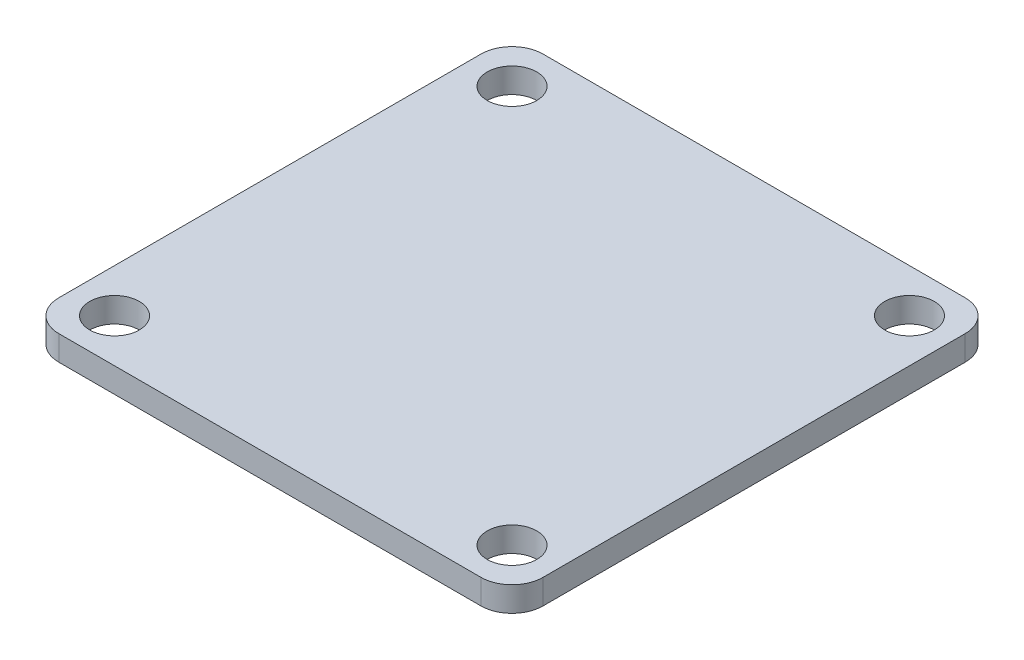
SolidWorks part; units mm, degrees
material "СТ3КП"
ref_plane "Спереди" through (0, 0, 0) normal (0, 0, 1) x (1, 0, 0)
ref_plane "Сверху" through (0, 0, 0) normal (0, 1, 0) x (1, 0, 0)
ref_plane "Справа" through (0, 0, 0) normal (1, 0, 0) x (0, 0, -1)
sketch "Эскиз1" plane through (0, 0, 0) normal (0, 1, 0) x (1, 0, 0)
  line L0 (-78.1421, -78.1421) -> (-78.1421, 78.1421) construction
  line L1 (-78.1421, -78.1421) -> (78.1421, -78.1421) construction
  line L2 (78.1421, -78.1421) -> (78.1421, 78.1421) construction
  line L3 (-78.1421, 78.1421) -> (78.1421, 78.1421) construction
  line L4 (-78.1421, -68.1421) -> (-78.1421, 68.1421)
  line L5 (-68.1421, -78.1421) -> (68.1421, -78.1421)
  line L6 (78.1421, -68.1421) -> (78.1421, 68.1421)
  line L7 (-68.1421, 78.1421) -> (68.1421, 78.1421)
  line L8 (0, 0) -> (64.1421, 64.1421) construction
  circle A0 centre (64.1421, 64.1421) radius 8 construction
  circle A1 centre (64.1421, 64.1421) radius 8
  arc A2 (68.1421, -78.1421) -> (78.1421, -68.1421) centre (68.1421, -68.1421) ccw
  arc A3 (-78.1421, -68.1421) -> (-68.1421, -78.1421) centre (-68.1421, -68.1421) ccw
  arc A4 (-78.1421, 68.1421) -> (-68.1421, 78.1421) centre (-68.1421, 68.1421) cw
  arc A5 (78.1421, 68.1421) -> (68.1421, 78.1421) centre (68.1421, 68.1421) ccw
  circle A6 centre (64.1421, -64.1421) radius 8
  circle A7 centre (-64.1421, -64.1421) radius 8
  circle A8 centre (-64.1421, 64.1421) radius 8
  point P28 (0, 0)
  dimension "D1" = 10
  dimension "D3" = 90.7107
  dimension "D2" = 4
base flange "Базовая кромка1" sketch "Эскиз1" thickness 8 reverse thickness direction yes parameters "D1"=1.5
sketch "Сгиб-Линии1" plane through (0, 0, 0) normal (0, 1, 0) x (1, 0, 0)
sketch "Граничная рамка1" plane through (0, 0, 0) normal (0, 1, 0) x (1, 0, 0)
sheet metal parameters "Листовой металл3" thickness 8 parameters "D1"=1.5
flat pattern "Развертка3" [suppressed]
sketch "Сгиб-Линии2" plane through (0, 0, 0) normal (0, 1, 0) x (1, 0, 0)
sketch "Граничная рамка2" [suppressed] plane through (0, 0, 0) normal (0, 1, 0) x (1, 0, 0)
